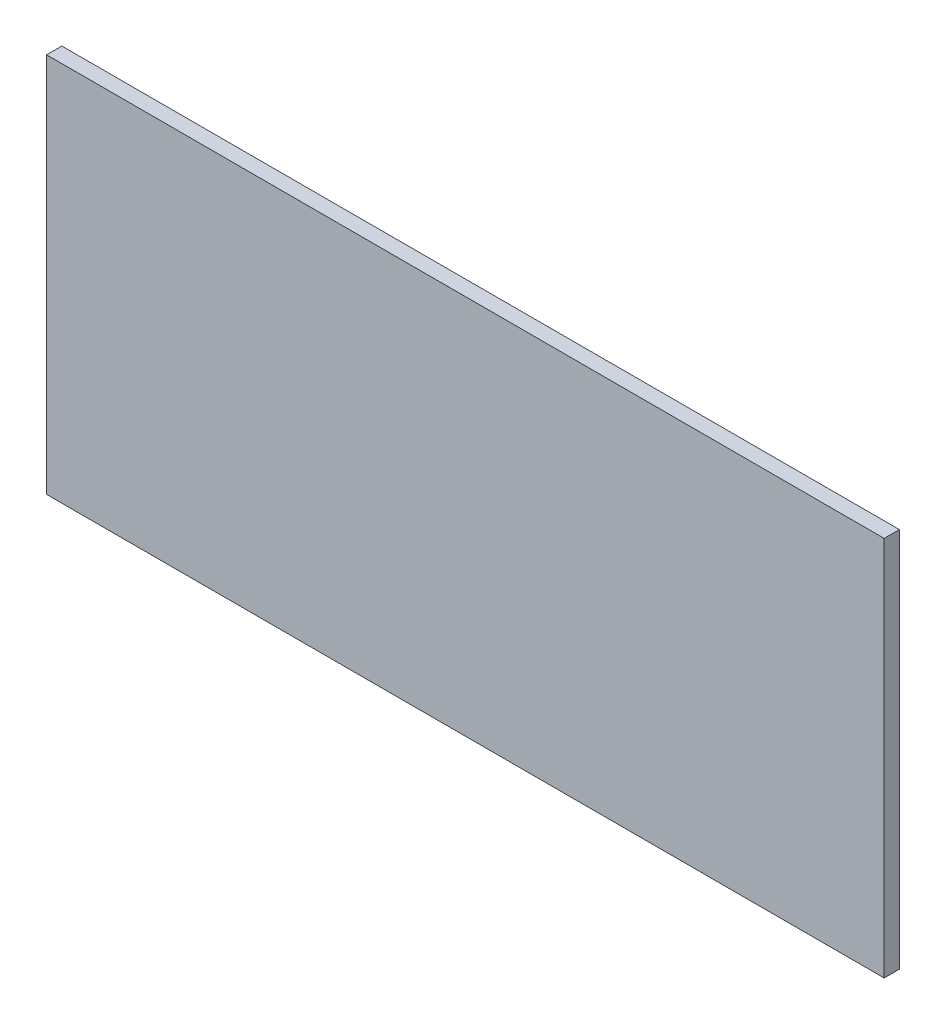
SolidWorks part; units mm, degrees
ref_plane "Front Plane" through (0, 0, 0) normal (0, 0, 1) x (1, 0, 0)
ref_plane "Top Plane" through (0, 0, 0) normal (0, 1, 0) x (1, 0, 0)
ref_plane "Right Plane" through (0, 0, 0) normal (1, 0, 0) x (0, 0, -1)
sketch "Sketch1" plane through (0, 0, 0) normal (0, 0, 1) x (1, 0, 0)
  line L1 (-27.5, -12.5) -> (27.5, -12.5)
  line L2 (-27.5, -12.5) -> (-27.5, 12.5)
  line L3 (-27.5, 12.5) -> (27.5, 12.5)
  line L4 (27.5, -12.5) -> (27.5, 12.5)
  line L5 (-27.5, -12.5) -> (27.5, 12.5) construction
  line L6 (-27.5, 12.5) -> (27.5, -12.5) construction
  point P0 (0, 0)
  dimension "D1" = 55
  dimension "D2" = 25
extrude "Boss-Extrude1" add sketch "Sketch1" along normal blind 1
